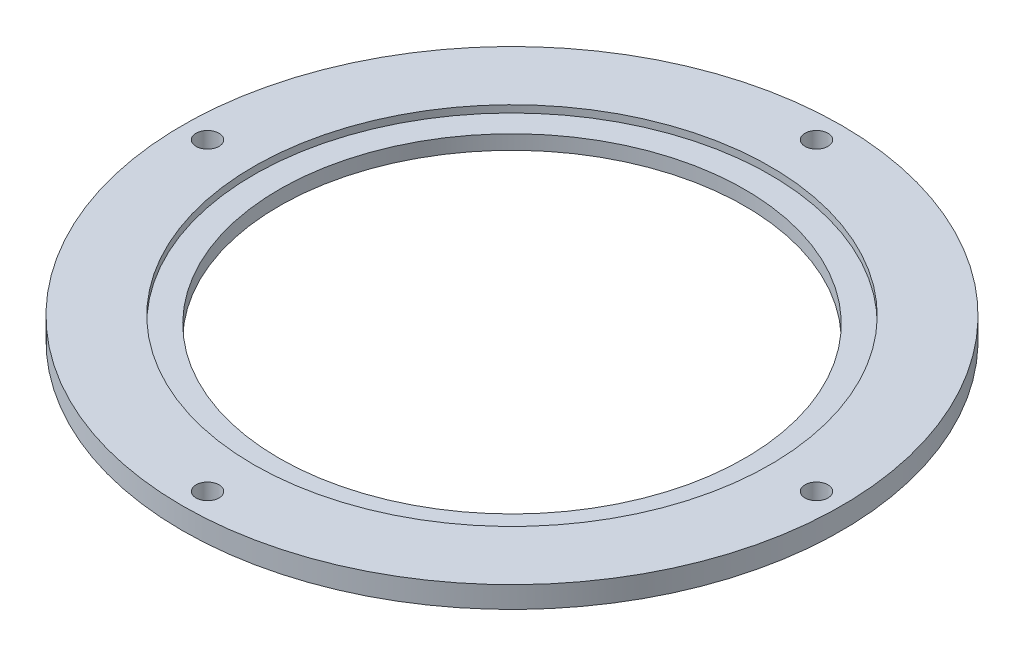
SolidWorks part; units mm, degrees
ref_plane "Front Plane" through (0, 0, 0) normal (0, 0, 1) x (1, 0, 0)
ref_plane "Top Plane" through (0, 0, 0) normal (0, 1, 0) x (1, 0, 0)
ref_plane "Right Plane" through (0, 0, 0) normal (1, 0, 0) x (0, 0, -1)
sketch "Sketch1" plane through (0, 0, 0) normal (0, 1, 0) x (1, 0, 0)
  circle A0 centre (0, 0) radius 46
  circle A1 centre (0, 0) radius 36.05
  circle A2 centre (0, 0) radius 32.5
  dimension "D1" = 92
  dimension "D2" = 72.1
  dimension "D3" = 65
extrude "Boss-Extrude1" add sketch "Sketch1" along normal blind 3 contours A0 A1 region at (-44.6989, 0, 0)
extrude "Boss-Extrude2" add sketch "Sketch1<3>" along normal blind 2 contours A1 A2 region at (-35.0304, 0, 0)
sketch "Sketch1<3>" plane through (0, 0, 0) normal (0, 1, 0) x (1, 0, 0) same geometry as "Sketch1"
hole_wizard "M3 Clearance Hole1" positions "Sketch2" profile "Sketch3" hole size "M3" standard "ANSI Metric" end condition through all
sketch "Sketch2" plane through (0, 3, 0) normal (0, 1, 0) x (1, 0, 0)
  line L1 (0, 0) -> (-42.5, 0) construction
  point P4 (-42.5, 0)
  dimension "D1" = 42.5
sketch "Sketch3" plane through (-42.5, 3, 0) normal (1, 0, 0) x (0, 0, 1)
  line L0 (0, 0) -> (0, 3)
  line L1 (0, 3) -> (1.6, 3)
  line L2 (1.6, 3) -> (1.6, 0)
  line L5 (1.6, 0) -> (0, 0)
  line L11 (0, -6.35) -> (0, 107.95) construction
  dimension "Thru Hole Dia." = 3.2
  dimension "Thru Hole Depth" = 3
pattern_circular "CirPattern1" count 4 over 360 about axis through (0, 3, 0) along (0, -1, 0) of "M3 Clearance Hole1" reverse direction yes
equation "\"Ratio\"= 15"
equation "\"Hull Diameter\"= 92"
equation "\"Fixed Ring Diameter\"= 76"
equation "\"Fixed Pin Diameter\"= 6"
equation "\"Output Ring Diameter\"= 40"
equation "\"Output Pin Diameter\"= 6"
equation "\"Disk Bearing Inner Diameter\"= 9"
equation "\"Disk Bearing Outer Diameter\"= 17"
equation "\"Disk Bearing Height\"= 5"
equation "\"Shaft Bearing Inner Diameter\"= 15"
equation "\"Shaft Bearing Outer Diameter\"= 21"
equation "\"Shaft Bearing Height\"= 4"
equation "\"Eccentricity\"= 1.5"
equation "\"Disk Height\"= 8"
equation "\"Disk Spacing\"= 5"
equation "\"Hull Height\"= 40"
equation "\"Shaft End Bearing Inner Diameter\"= 12"
equation "\"Shaft End Bearing Outer Diameter\"= 18"
equation "\"Shaft End Bearing Height\"= 4"
equation "\"Output Bearing Inner Diameter\"= 55"
equation "\"Output Bearing Outer Diameter\"= 72"
equation "\"Outer Bearing Height\"= 9"
equation "\"D1@Sketch1\"=\"Hull Diameter\""
equation "\"D2@Sketch1\"=\"Output Bearing Outer Diameter\"+0.1"
equation "\"D3@Sketch1\"=\"Output Bearing Inner Diameter\"+10"
